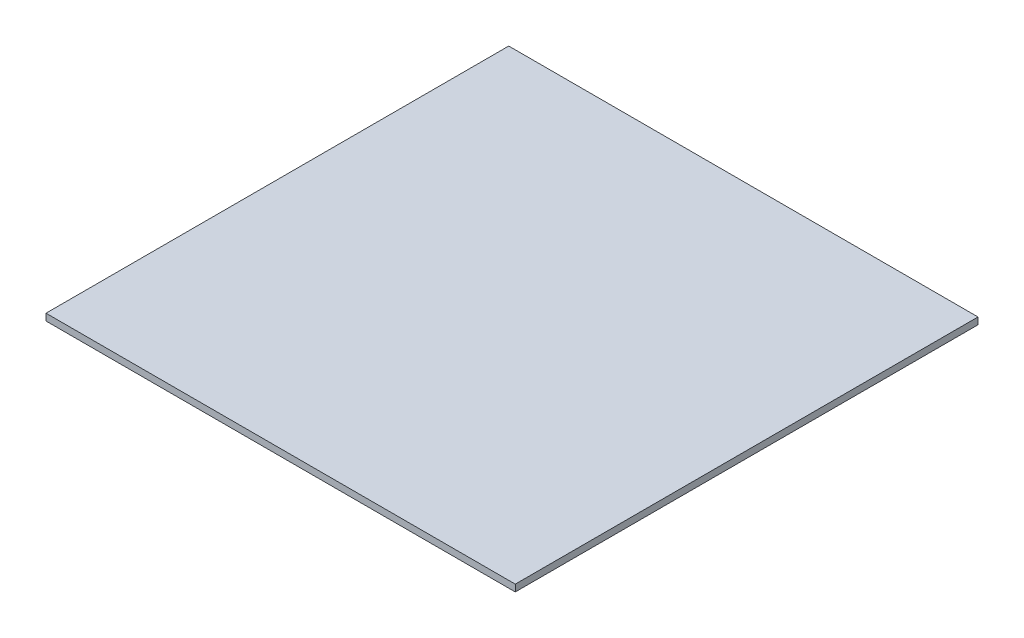
SolidWorks part; units mm, degrees
material "Polyethylene Cross-Linked"
ref_plane "Front Plane" through (0, 0, 0) normal (0, 0, 1) x (1, 0, 0)
ref_plane "Top Plane" through (0, 0, 0) normal (0, 1, 0) x (1, 0, 0)
ref_plane "Right Plane" through (0, 0, 0) normal (1, 0, 0) x (0, 0, -1)
sketch "Sketch1" plane through (0, 0, 0) normal (0, 1, 0) x (1, 0, 0)
  line L1 (0, 0) -> (218.948, 0)
  line L3 (0, 215.9) -> (218.948, 215.9)
  line L8 (218.948, 215.9) -> (218.948, 0)
  line L41 (0, 0) -> (0, 215.9)
extrude "Boss-Extrude1" add sketch "Sketch1" along normal blind 3.175
ref_plane "Plane1" through (218.948, 3.175, -215.9) normal (-1, 0, 0) x (0, 0, 1)
